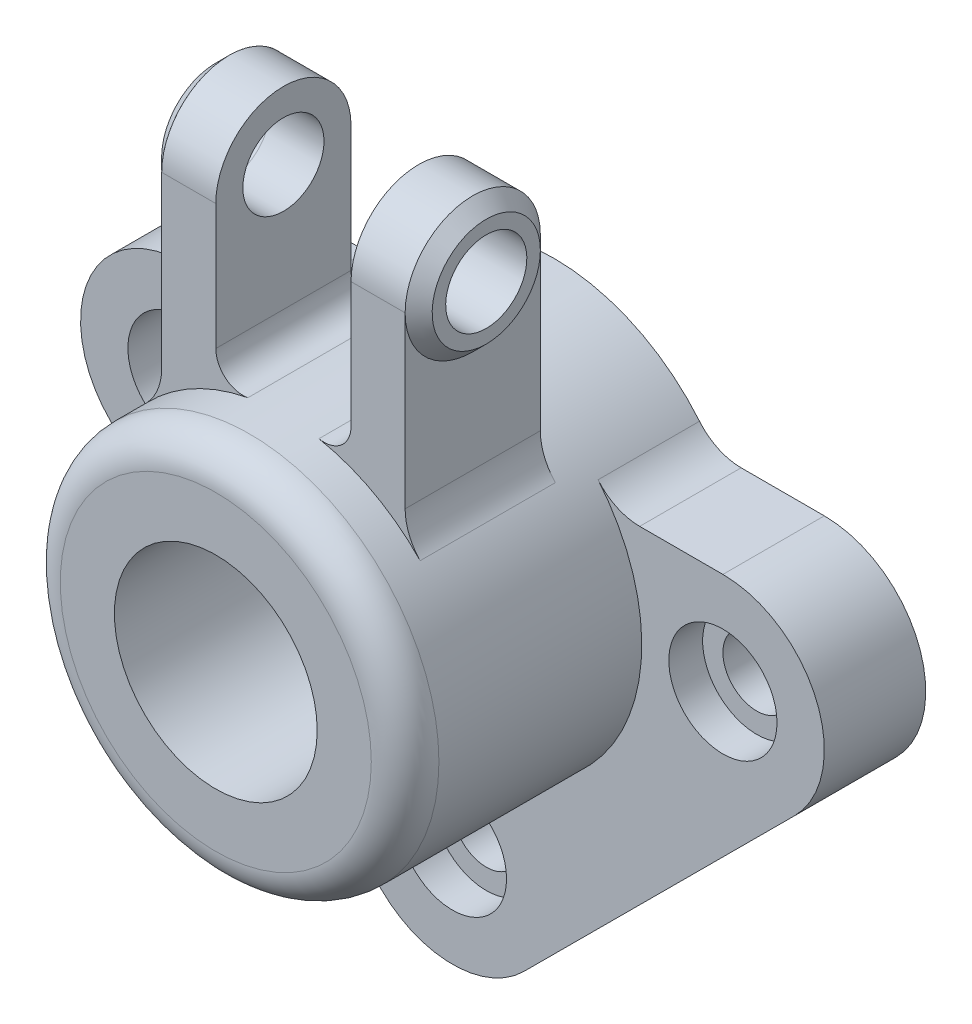
SolidWorks part; units mm, degrees
ref_plane "Ön Düzlem" through (0, 0, 0) normal (0, 0, 1) x (1, 0, 0)
ref_plane "Üst Düzlem" through (0, 0, 0) normal (0, 1, 0) x (1, 0, 0)
ref_plane "Sağ Düzlem" through (0, 0, 0) normal (1, 0, 0) x (0, 0, -1)
sketch "Çizim1" plane through (0, 0, 0) normal (0, 0, 1) x (1, 0, 0)
  line L0 (-10.5569, -50.5776) -> (-50.5962, -10.617)
  line L1 (0, 0) -> (0, -40) construction
  line L2 (10.5569, -50.5776) -> (50.5962, -10.617)
  line L3 (-40, 15) -> (-27.6948, 15)
  line L4 (40, 15) -> (27.6948, 15)
  circle A8 centre (0, 0) radius 15
  arc A9 (-40, 15) -> (-50.5962, -10.617) centre (-40, 0) ccw
  circle A10 centre (-40, 0) radius 5
  circle A11 centre (40, 0) radius 5
  arc A12 (40, 15) -> (50.5962, -10.617) centre (40, 0) cw
  arc A13 (-10.5569, -50.5776) -> (10.5569, -50.5776) centre (0, -40) ccw
  arc A14 (-27.6948, 15) -> (-21.5404, 17.8889) centre (-27.6948, 23) ccw
  arc A15 (27.6948, 15) -> (21.5404, 17.8889) centre (27.6948, 23) cw
  arc A16 (21.5404, 17.8889) -> (-21.5404, 17.8889) centre (0, 0) ccw
  point P20 (0, 0)
  point P21 (0, 0)
  dimension "D4" = 30
  dimension "D5" = 10
  dimension "D6" = 40
  dimension "D7" = 8
  dimension "D1" = 30
  dimension "D3" = 40
extrude "Yükseklik-Ekstrüzyon1" add sketch "Çizim1" along normal blind 15
sketch "Çizim2" plane through (0, 0, 15) normal (0, 0, 1) x (1, 0, 0)
  circle A0 centre (0, 0) radius 28
  circle A1 centre (0, 0) radius 15
  dimension "D1" = 56
extrude "Yükseklik-Ekstrüzyon2" add sketch "Çizim2" along normal blind 35
fillet "Radyus1" radius 5 1 edges at (28, 0, 50)
sketch "Çizim3" plane through (0, 0, 15) normal (0, 0, 1) x (1, 0, 0)
  circle A0 centre (0, -40) radius 5
  dimension "D1" = 10
  dimension "D2" = 40
extrude "Kes-Ekstrüzyon1" cut sketch "Çizim3" against normal up to surface (15 mm away) up to face at (0, -1.5156, 0)
sketch "Çizim4" plane through (0, 0, 15) normal (0, 0, 1) x (1, 0, 0)
  circle A0 centre (-40, 0) radius 8
  circle A1 centre (0, -40) radius 8
  circle A2 centre (40, 0) radius 8
  dimension "D1" = 16
extrude "Kes-Ekstrüzyon2" cut sketch "Çizim4" against normal blind 5
ref_plane "Düzlem1" through (0, 0, 40) normal (0, 0, 1) x (1, 0, 0)
sketch "Çizim5" plane through (0, 0, 40) normal (0, 0, 1) x (1, 0, 0)
  line L0 (0, 63.1906) -> (0, 0) construction
  line L1 (-18, 60) -> (-18, 24.8998)
  line L2 (-18, 60) -> (-10, 60)
  line L3 (-10, 60) -> (-10, 31.4325)
  arc A0 (-18, 24.8998) -> (-20.2222, 19.3665) centre (-26, 24.8998) cw
  circle A1 centre (0, 0) radius 28 construction
  arc A2 (-10, 31.4325) -> (-5.25, 27.5034) centre (-6, 31.4325) ccw
  arc A3 (-5.25, 27.5034) -> (-20.2222, 19.3665) centre (0, 0) ccw
  point P13 (0, 0)
  point P14 (-20.2222, 19.3665)
  point P15 (-20.2222, 19.3665)
  point P16 (0, 0)
  point P19 (0, 0)
  point P20 (0, 0)
  dimension "D1" = 8
  dimension "D2" = 4
  dimension "D3" = 8
  dimension "D4" = 10
  dimension "D5" = 60
extrude "Yükseklik-Ekstrüzyon3" add sketch "Çizim5" against normal blind 20 contours L3 A2 A3 A0 L1 L2
sketch "Çizim6" plane through (-18, 0, 0) normal (-1, 0, 0) x (0, 0, 1)
  line L0 (40, 60) -> (40, 24.8998) construction
  line L1 (20, 60) -> (40, 60) construction
  line L2 (20, 60) -> (20, 24.8998) construction
  line L3 (40, 60) -> (40, 50)
  line L4 (20, 60) -> (40, 60)
  line L5 (20, 60) -> (20, 50)
  circle A0 centre (30, 50) radius 6
  arc A1 (40, 50) -> (20, 50) centre (30, 50) ccw
  line M2 (40, 24.8998) -> (40, 60)
  line M3 (40, 60) -> (20, 60)
  line M4 (20, 60) -> (20, 24.8998)
  dimension "D1" = 12
  dimension "D2" = 50
extrude "Kes-Ekstrüzyon3" cut sketch "Çizim6" against normal up to surface (8 mm away) contours A1 M2 M3 | A1 L4 M4 | A0 up to face at (-10, 45.7162, 30)
sketch "Çizim7" plane through (-18, 0, 0) normal (-1, 0, 0) x (0, 0, 1)
  circle A0 centre (30, 50) radius 6 construction
  circle A1 centre (30, 50) radius 6
  circle A2 centre (30, 50) radius 10
extrude "Yükseklik-Ekstrüzyon4" add sketch "Çizim7" along normal blind 2 separate body
chamfer "Pah1" distance 2 angle 45 1 edges at (-20, 40, 30)
mirror "Aynalama1" about plane through (0, 0, 0) normal (1, 0, 0) of "Pah1", "Yükseklik-Ekstrüzyon4", "Kes-Ekstrüzyon3", "Yükseklik-Ekstrüzyon3"
